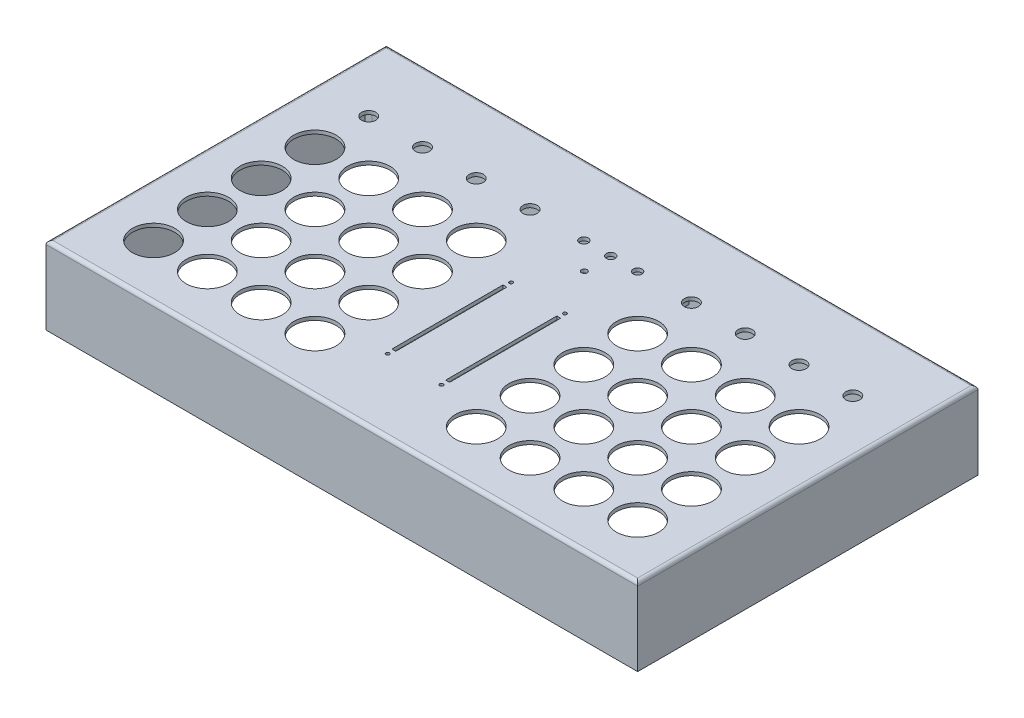
SolidWorks part; units mm, degrees
material "ABS"
ref_plane "Front Plane" through (0, 0, 0) normal (0, 0, 1) x (1, 0, 0)
ref_plane "Top Plane" through (0, 0, 0) normal (0, 1, 0) x (1, 0, 0)
ref_plane "Right Plane" through (0, 0, 0) normal (1, 0, 0) x (0, 0, -1)
sketch "Sketch2" plane through (0, 0, 0) normal (0, 1, 0) x (1, 0, 0)
  line L0 (0, 0) -> (91.5, 0) construction
  line L1 (0, 0) -> (0, 91.5) construction
  line L2 (122, 80.75) -> (122, 10.75) construction
  line L3 (120.9, 77.25) -> (123.1, 77.25)
  line L4 (120.9, 77.25) -> (120.9, 14.25)
  line L5 (120.9, 14.25) -> (123.1, 14.25)
  line L6 (123.1, 77.25) -> (123.1, 14.25)
  line L7 (91.5, 45.75) -> (137.25, 45.75) construction
  line L8 (91.5, 30.5) -> (91.5, 61) construction
  line L9 (0, 91.5) -> (0, 122) construction
  line L10 (0, 122) -> (91.5, 122) construction
  line L11 (0, 122) -> (30.5, 122) construction
  line L12 (137.25, -28.4189) -> (137.25, 162.5507) construction
  line L13 (274.5, 122) -> (244, 122) construction
  line L14 (274.5, 122) -> (183, 122) construction
  line L15 (274.5, 91.5) -> (274.5, 122) construction
  line L16 (183, 30.5) -> (183, 61) construction
  line L17 (152.5, 80.75) -> (152.5, 10.75) construction
  line L18 (274.5, 0) -> (274.5, 91.5) construction
  line L19 (274.5, 0) -> (183, 0) construction
  line L20 (151.4, 77.25) -> (151.4, 14.25)
  line L21 (153.6, 14.25) -> (151.4, 14.25)
  line L22 (153.6, 77.25) -> (153.6, 14.25)
  line L23 (153.6, 77.25) -> (151.4, 77.25)
  line L25 (-30.5, -30.5) -> (305, -30.5)
  line L26 (-30.5, -30.5) -> (-30.5, 162.5)
  line L27 (-30.5, 162.5) -> (305, 162.5)
  line L28 (305, -30.5) -> (305, 162.5)
  circle A0 centre (0, 0) radius 12
  circle A1 centre (30.5, 0) radius 12
  circle A2 centre (61, 0) radius 12
  circle A3 centre (91.5, 0) radius 12
  circle A4 centre (30.5, 30.5) radius 12
  circle A5 centre (61, 30.5) radius 12
  circle A6 centre (91.5, 30.5) radius 12
  circle A7 centre (30.5, 61) radius 12
  circle A8 centre (61, 61) radius 12
  circle A9 centre (91.5, 61) radius 12
  circle A10 centre (30.5, 91.5) radius 12
  circle A11 centre (61, 91.5) radius 12
  circle A12 centre (91.5, 91.5) radius 12
  circle A13 centre (0, 30.5) radius 12
  circle A14 centre (0, 61) radius 12
  circle A15 centre (0, 91.5) radius 12
  circle A16 centre (122, 80.75) radius 1
  circle A17 centre (122, 10.75) radius 1
  circle A18 centre (0, 122) radius 4
  circle A19 centre (30.5, 122) radius 4
  circle A20 centre (61, 122) radius 4
  circle A21 centre (91.5, 122) radius 4
  circle A22 centre (183, 122) radius 4
  circle A23 centre (213.5, 122) radius 4
  circle A24 centre (244, 122) radius 4
  circle A25 centre (274.5, 122) radius 4
  circle A26 centre (152.5, 10.75) radius 1
  circle A27 centre (152.5, 80.75) radius 1
  circle A28 centre (274.5, 91.5) radius 12
  circle A29 centre (274.5, 61) radius 12
  circle A30 centre (274.5, 30.5) radius 12
  circle A31 centre (183, 91.5) radius 12
  circle A32 centre (213.5, 91.5) radius 12
  circle A33 centre (244, 91.5) radius 12
  circle A34 centre (183, 61) radius 12
  circle A35 centre (213.5, 61) radius 12
  circle A36 centre (244, 61) radius 12
  circle A37 centre (183, 30.5) radius 12
  circle A38 centre (213.5, 30.5) radius 12
  circle A39 centre (244, 30.5) radius 12
  circle A40 centre (183, 0) radius 12
  circle A41 centre (213.5, 0) radius 12
  circle A42 centre (244, 0) radius 12
  circle A43 centre (274.5, 0) radius 12
  point P41 (122, 77.25)
  point P42 (120.9, 45.75)
  point P105 (153.6, 45.75)
  point P106 (152.5, 77.25)
  dimension "D1" = 24
  dimension "D8" = 2
  dimension "D12" = 8
  dimension "D4" = 30.5
  dimension "D5" = 30.5
  dimension "D6" = 63
  dimension "D7" = 2.2
  dimension "D9" = 3.5
  dimension "D10" = 3.5
  dimension "D11" = 30.5
  dimension "D14" = 30.5
  dimension "D15" = 30.5
  dimension "D16" = 15.25
  dimension "D17" = 30.5
  dimension "D18" = 30.5
  dimension "D19" = 30.5
  dimension "D20" = 40.5
  dimension "D2" = 4
  dimension "D3" = 4
  dimension "D13" = 4
extrude "Boss-Extrude1" add sketch "Sketch2" along normal blind 44
shell "Shell1" thickness 2 removed face at (244, 0, -12) removed face at (0, 44, 12) removed face at (30.5, 44, 12) removed face at (61, 44, 12) removed face at (91.5, 44, 12) removed face at (91.5, 44, -18.5) removed face at (61, 44, -18.5) removed face at (30.5, 44, -18.5) removed face at (0, 44, -18.5) removed face at (0, 44, -49) removed face at (0, 44, -79.5) removed face at (30.5, 44, -79.5) removed face at (30.5, 44, -49) removed face at (61, 44, -49) removed face at (61, 44, -79.5) removed face at (91.5, 44, -79.5) removed face at (91.5, 44, -49) removed face at (0, 44, -118) removed face at (30.5, 44, -118) removed face at (91.5, 44, -118) removed face at (61, 44, -118) removed face at (122, 44, -79.75) removed face at (152.5, 44, -81.75) removed face at (183, 44, -126) removed face at (183, 44, -103.5) removed face at (213.5, 44, -103.5) removed face at (213.5, 44, -126) removed face at (183, 44, -73) removed face at (183, 44, -42.5) removed face at (183, 44, -12) removed face at (213.5, 44, -12) removed face at (213.5, 44, -42.5) removed face at (213.5, 44, -73) removed face at (244, 44, -73) removed face at (244, 44, -42.5) removed face at (244, 44, -12) removed face at (274.5, 44, -12) removed face at (274.5, 44, -42.5) removed face at (274.5, 44, -73) removed face at (274.5, 44, -103.5) removed face at (244, 44, -103.5) removed face at (244, 44, -126) removed face at (274.5, 44, -126) removed face at (152.5, 44, -11.75) removed face at (122, 44, -9.75) removed face at (153.6, 22, -45.75) removed face at (152.5, 22, -77.25) removed face at (122, 22, -77.25) removed face at (123.1, 22, -45.75) removed face at (120.9, 22, -45.75) removed face at (122, 22, -14.25) removed face at (151.4, 22, -45.75) removed face at (152.5, 22, -14.25)
fillet "Fillet1" radius 2 4 edges at (-30.5, 44, -66) (137.25, 44, 30.5) (305, 44, -66) (137.25, 44, -162.5)
sketch "Sketch3" plane through (0, 44, 0) normal (0, 1, 0) x (1, 0, 0)
  line L0 (91.5, 122) -> (183, 122) construction
  line L1 (137.25, 160.5) -> (137.25, 122) construction
  line L2 (303, 160.5) -> (-28.5, 160.5) construction
  line L3 (122, 80.75) -> (122, 122) construction
  line L4 (152.5, 122) -> (152.5, 80.75) construction
  line L5 (137.25, 122) -> (137.25, 107) construction
  circle A0 centre (122, 122) radius 2.5
  circle A1 centre (137.25, 122) radius 2.5
  circle A2 centre (152.5, 122) radius 2.5
  circle A3 centre (137.25, 107) radius 1.6
  dimension "D1" = 5
  dimension "D2" = 3.2
  dimension "D3" = 15
extrude "Cut-Extrude1" cut sketch "Sketch3" against normal blind 10
sketch "Sketch4" plane through (0, 42, 0) normal (0, -1, 0) x (1, 0, 0)
  line L0 (117.25, -107) -> (157.25, -107) construction
  circle A0 centre (157.25, -107) radius 4
  circle A1 centre (137.25, -107) radius 1.6 construction
  circle A3 centre (137.25, -107) radius 1.6559 construction
  circle A4 centre (117.25, -107) radius 4
  dimension "D1" = 20
  dimension "D3" = 8
  dimension "D6" = 8
extrude "Boss-Extrude2" add sketch "Sketch4" along normal blind 5
fillet "Fillet2" radius 1 2 edges at (157.25, 42, -111) (117.25, 42, -111)
sketch "Sketch5" plane through (0, 37, 0) normal (0, -1, 0) x (1, 0, 0)
  circle A0 centre (117.25, -107) radius 1.75
  circle A1 centre (157.25, -107) radius 1.75
  dimension "D1" = 3.5
  dimension "D2" = 3.5
extrude "Cut-Extrude2" cut sketch "Sketch5" against normal blind 4
sketch "Sketch6" plane through (0, 0, 0) normal (0, -1, 0) x (1, 0, 0)
  line L0 (-22.5, 28.5) -> (-22.5, -160.5) construction
  line L1 (-28.5, 28.5) -> (303, 28.5) construction
  line L2 (303, -160.5) -> (-28.5, -160.5) construction
  line L3 (-28.5, -160.5) -> (-28.5, 28.5) construction
  line L4 (297, 30.5) -> (297, -160.5) construction
  line L5 (-30.5, 30.5) -> (305, 30.5) construction
  line L6 (303, -154.5) -> (-28.5, -154.5) construction
  line L7 (303, 28.5) -> (303, -160.5) construction
  line L8 (-28.5, -160.5) -> (-28.5, 28.5) construction
  line L9 (-28.5, 22.5) -> (303, 22.5) construction
  line L10 (303, 28.5) -> (303, -160.5) construction
  line L11 (-28.5, 28.5) -> (303, 28.5) construction
  line L12 (303, -160.5) -> (-28.5, -160.5) construction
  line L14 (-24.5, 16.5) -> (-28.5, 16.5)
  line L15 (-16.5, 24.5) -> (-16.5, 28.5)
  line L16 (-16.5, 28.5) -> (-28.5, 28.5)
  line L17 (-28.5, 16.5) -> (-28.5, 28.5)
  line L18 (-16.5, 16.5) -> (-28.5, 28.5) construction
  line L19 (-16.5, 28.5) -> (-28.5, 16.5) construction
  line L20 (-24.5, -148.5) -> (-28.5, -148.5)
  line L21 (-16.5, -156.5) -> (-16.5, -160.5)
  line L22 (-16.5, -160.5) -> (-28.5, -160.5)
  line L23 (-28.5, -148.5) -> (-28.5, -160.5)
  line L24 (-16.5, -148.5) -> (-28.5, -160.5) construction
  line L25 (-16.5, -160.5) -> (-28.5, -148.5) construction
  line L26 (299, -148.5) -> (303, -148.5)
  line L27 (291, -156.5) -> (291, -160.5)
  line L28 (291, -160.5) -> (303, -160.5)
  line L29 (303, -148.5) -> (303, -160.5)
  line L30 (291, -148.5) -> (303, -160.5) construction
  line L31 (291, -160.5) -> (303, -148.5) construction
  line L32 (299, 16.5) -> (303, 16.5)
  line L33 (291, 24.5) -> (291, 28.5)
  line L34 (291, 28.5) -> (303, 28.5)
  line L35 (303, 16.5) -> (303, 28.5)
  line L36 (291, 16.5) -> (303, 28.5) construction
  line L37 (291, 28.5) -> (303, 16.5) construction
  line L38 (137.15, 16.5) -> (137.35, 16.5)
  line L39 (131.25, 22.4) -> (131.25, 28.5)
  line L40 (131.25, 28.5) -> (143.25, 28.5)
  line L41 (143.25, 22.4) -> (143.25, 28.5)
  line L42 (131.25, 16.5) -> (143.25, 28.5) construction
  line L43 (131.25, 28.5) -> (143.25, 16.5) construction
  line L44 (137.15, -148.5) -> (137.35, -148.5)
  line L45 (131.25, -154.4) -> (131.25, -160.5)
  line L46 (131.25, -160.5) -> (143.25, -160.5)
  line L47 (143.25, -154.4) -> (143.25, -160.5)
  line L48 (131.25, -148.5) -> (143.25, -160.5) construction
  line L49 (131.25, -160.5) -> (143.25, -148.5) construction
  circle A0 centre (-22.5, -154.5) radius 2 construction
  circle A1 centre (297, -154.5) radius 2 construction
  circle A2 centre (137.25, -154.5) radius 2 construction
  circle A3 centre (-22.5, 22.5) radius 2 construction
  circle A4 centre (137.25, 22.5) radius 2 construction
  circle A5 centre (297, 22.5) radius 2 construction
  arc A6 (-24.5, 16.5) -> (-16.5, 24.5) centre (-24.5, 24.5) ccw
  arc A7 (299, 16.5) -> (291, 24.5) centre (299, 24.5) cw
  arc A8 (299, -148.5) -> (291, -156.5) centre (299, -156.5) ccw
  arc A9 (-24.5, -148.5) -> (-16.5, -156.5) centre (-24.5, -156.5) cw
  arc A10 (137.15, 16.5) -> (131.25, 22.4) centre (137.15, 22.4) cw
  arc A11 (137.35, 16.5) -> (143.25, 22.4) centre (137.35, 22.4) ccw
  arc A12 (137.35, -148.5) -> (143.25, -154.4) centre (137.35, -154.4) cw
  arc A13 (137.15, -148.5) -> (131.25, -154.4) centre (137.15, -154.4) ccw
  point P30 (297, -154.5)
  point P31 (297, 22.5)
  point P32 (-22.5, 22.5)
  point P33 (137.25, 22.5)
  point P34 (137.25, -154.5)
  point P35 (-22.5, -154.5)
  dimension "D5" = 4
  dimension "D6" = 8
  dimension "D9" = 8
  dimension "D10" = 5.9
  dimension "D1" = 6
  dimension "D2" = 6
  dimension "D3" = 6
  dimension "D4" = 6
  dimension "D7" = 12
  dimension "D8" = 12
extrude "Boss-Extrude3" add sketch "Sketch6" against normal blind 20 from offset 4 offset against normal yes
sketch "Sketch7" plane through (0, 0, 0) normal (0, -1, 0) x (1, 0, 0)
  circle A0 centre (-22.5, 22.5) radius 1.75
  circle A1 centre (137.25, 22.5) radius 1.75
  circle A2 centre (297, 22.5) radius 1.75
  circle A3 centre (297, -154.5) radius 1.75
  circle A4 centre (137.25, -154.5) radius 1.75
  circle A5 centre (-22.5, -154.5) radius 1.75
  dimension "D1" = 3.5
extrude "Cut-Extrude3" cut sketch "Sketch7" against normal blind 10
